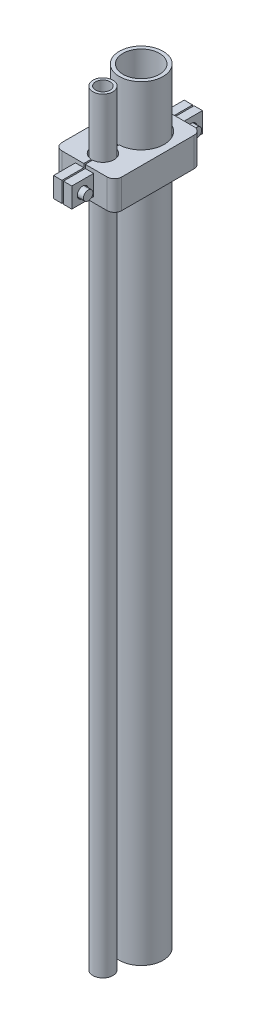
SolidWorks part; units mm, degrees
ref_plane "Alzado" through (0, 0, 0) normal (0, 0, 1) x (1, 0, 0)
ref_plane "Planta" through (0, 0, 0) normal (0, 1, 0) x (1, 0, 0)
ref_plane "Vista lateral" through (0, 0, 0) normal (1, 0, 0) x (0, 0, -1)
sketch "Croquis1" plane through (0, 0, 0) normal (0, 1, 0) x (1, 0, 0)
  line L0 (0, 0) -> (0, -52.5) construction
  circle A0 centre (0, 0) radius 25
  circle A1 centre (0, 0) radius 30
  circle A2 centre (0, -52.5) radius 10
  circle A3 centre (0, -52.5) radius 13.75
  dimension "D1" = 60
  dimension "D2" = 5
  dimension "D3" = 20
  dimension "D4" = 27.5
  dimension "D5" = 52.5
extrude "Saliente-Extruir1" add sketch "Croquis1" along normal blind 1050
ref_plane "Plano1" through (0, 950, 0) normal (0, 1, 0) x (1, 0, 0)
sketch "Croquis2" plane through (0, 950, 0) normal (0, 1, 0) x (1, 0, 0)
  line L0 (-41, 0) -> (41, 0) construction
  line L5 (-12.5, 71.4841) -> (-1, 71.4841)
  line L6 (-41, 31.4841) -> (-41, -67.7172)
  line L7 (-12.5, -107.7172) -> (-1, -107.7172)
  line L8 (41, 31.4841) -> (41, -67.7172)
  line L9 (0, 71.4841) -> (0, -107.7172) construction
  line L10 (-31, -77.7172) -> (-12.5, -77.7172)
  line L11 (-12.5, -77.7172) -> (-12.5, -107.7172)
  line L12 (31, -77.7172) -> (12.5, -77.7172)
  line L13 (12.5, -77.7172) -> (12.5, -107.7172)
  line L14 (-31, 41.4841) -> (-12.5, 41.4841)
  line L15 (-12.5, 41.4841) -> (-12.5, 71.4841)
  line L16 (31, 41.4841) -> (12.5, 41.4841)
  line L17 (12.5, 41.4841) -> (12.5, 71.4841)
  line L18 (-41, -52.5) -> (41, -52.5) construction
  line L19 (1, 71.4841) -> (1, 31.4841)
  line L20 (-1, 71.4841) -> (-1, 31.4841)
  line L21 (1, -31.4841) -> (1, -37.2828)
  line L22 (-1, -31.4841) -> (-1, -37.2828)
  line L23 (1, -67.7172) -> (1, -107.7172)
  line L24 (-1, -67.7172) -> (-1, -107.7172)
  line L25 (1, -107.7172) -> (12.5, -107.7172)
  line L26 (1, 71.4841) -> (12.5, 71.4841)
  arc A2 (-31, 41.4841) -> (-41, 31.4841) centre (-31, 31.4841) ccw
  arc A3 (-1, 31.4841) -> (-1, -31.4841) centre (0, 0) ccw
  circle A4 centre (0, 0) radius 30 construction
  arc A5 (31, 41.4841) -> (41, 31.4841) centre (31, 31.4841) cw
  arc A6 (-1, -37.2828) -> (-1, -67.7172) centre (0, -52.5) ccw
  circle A7 centre (0, -52.5) radius 13.75 construction
  arc A8 (-31, -77.7172) -> (-41, -67.7172) centre (-31, -67.7172) cw
  arc A9 (31, -77.7172) -> (41, -67.7172) centre (31, -67.7172) ccw
  arc A10 (1, -31.4841) -> (1, 31.4841) centre (0, 0) ccw
  arc A11 (1, -67.7172) -> (1, -37.2828) centre (0, -52.5) ccw
  point P8 (0, 0)
  point P15 (0, -52.5)
  point P19 (0, 0)
  point P45 (-1, -34.3835)
  dimension "D1" = 2
  dimension "D2" = 1.5
  dimension "D3" = 40
  dimension "D4" = 1.5
  dimension "D5" = 25
  dimension "D10" = 10
  dimension "D6" = 10
  dimension "D7" = 10
  dimension "D8" = 30
  dimension "D9" = 30
extrude "Saliente-Extruir2" add sketch "Croquis2" along normal mid plane 40 separate body
sketch "Croquis4" plane through (0, 0, 0) normal (1, 0, 0) x (0, 0, -1)
  line L0 (97.1269, 950) -> (-97.1269, 950) construction
  line L1 (-107.7172, 970) -> (-107.7172, 930) construction
  line L2 (-77.7172, 970) -> (-77.7172, 930) construction
  line L3 (71.4841, 970) -> (71.4841, 930) construction
  line L4 (-77.7172, 965) -> (-107.7172, 965)
  line L5 (-77.7172, 965) -> (-77.7172, 970)
  line L6 (-77.7172, 930) -> (-107.7172, 930)
  line L7 (-77.7172, 930) -> (-77.7172, 937.5)
  line L8 (-77.7172, 937.5) -> (-107.7172, 937.5)
  line L9 (-107.7172, 930) -> (-107.7172, 937.5)
  line L10 (-77.7172, 970) -> (-107.7172, 970)
  line L11 (-107.7172, 965) -> (-107.7172, 970)
  line L13 (41.4841, 930) -> (71.4841, 930)
  line L14 (41.4841, 930) -> (41.4841, 937.5)
  line L15 (41.4841, 937.5) -> (71.4841, 937.5)
  line L16 (71.4841, 930) -> (71.4841, 937.5)
  line L17 (41.4841, 970) -> (71.4841, 970)
  line L18 (41.4841, 970) -> (41.4841, 965)
  line L19 (41.4841, 965) -> (71.4841, 965)
  line L20 (71.4841, 970) -> (71.4841, 965)
  circle A0 centre (56.4841, 950) radius 7.5
  circle A1 centre (-92.7172, 950) radius 7.5
  circle A2 centre (-92.7172, 950) radius 6.5
  circle A3 centre (56.4841, 950) radius 6.5
  dimension "D3" = 15
  dimension "D4" = 1
  dimension "D5" = 1
  dimension "D1" = 15
  dimension "D2" = 15
  dimension "D6" = 5
  dimension "D7" = 7.5
extrude "Cortar-Extruir1" cut sketch "Croquis4" against normal mid plane 40 contours A0 | A1 | L7 L6 L9 L8 | L5 L4 L11 L10 | L18 L17 L20 L19 | L14 L13 L16 L15
extrude "Saliente-Extruir3" add sketch "Croquis4<4>" along normal mid plane 40 separate body contours A3 | A2 region at (0, 950, 92.7172) region at (0, 950, -56.4841)
sketch "Croquis4<4>" plane through (0, 0, 0) normal (1, 0, 0) x (0, 0, -1) same geometry as "Croquis4"
